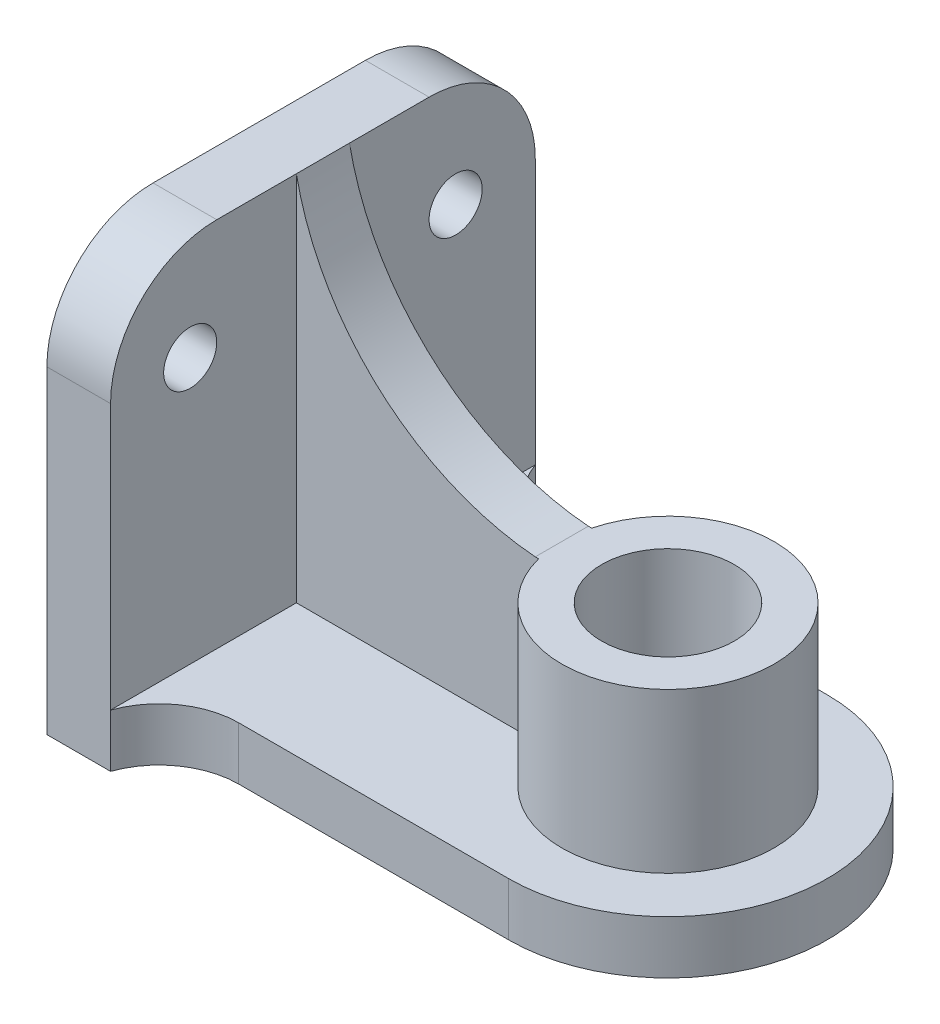
SolidWorks part; units mm, degrees
ref_plane "Front Plane" through (0, 0, 0) normal (0, 0, 1) x (1, 0, 0)
ref_plane "Top Plane" through (0, 0, 0) normal (0, 1, 0) x (1, 0, 0)
ref_plane "Right Plane" through (0, 0, 0) normal (1, 0, 0) x (0, 0, -1)
sketch "Sketch1" plane through (0, 0, 0) normal (0, 1, 0) x (1, 0, 0)
  line L0 (0, 0) -> (0, -80)
  line L1 (0, -80) -> (12, -80)
  line L2 (12, -80) -> (12, 0)
  line L3 (12, 0) -> (0, 0)
  line L4 (77, -1039.1946) -> (77, 48960.8054) construction
  line L5 (-107, -40) -> (107, -40)
  line L6 (77, -70) -> (26.1421, -70)
  line L7 (77, -10) -> (26.1421, -10)
  circle A0 centre (77, -40) radius 20
  circle A1 centre (77, -40) radius 12.5
  arc A2 (77, -70) -> (77, -10) centre (77, -40) ccw
  arc A4 (26.1421, -70) -> (12, -80) centre (26.1421, -85) ccw
  arc A5 (26.1421, -10) -> (12, 0) centre (26.1421, 5) cw
  point P10 (0, -40)
  dimension "D4" = 40
  dimension "D5" = 25
  dimension "D6" = 60
  dimension "D7" = 15
  dimension "D1" = 80
  dimension "D2" = 12
  dimension "D3" = 65
extrude "Boss-Extrude3" add sketch "Sketch1" along normal blind 10 contours L6 L4 A0 L5 L2 A4 | A0 L4 L7 A5 L2 L5 | L4 A0 L5 A2 | L4 A2 L5 A0 region at (39.3253, 0, 23.3734) region at (39.3253, 0, 56.6266) region at (93.1277, 0, 23.8723) region at (93.1277, 0, 56.1277)
extrude "Boss-Extrude4" add sketch "Sketch1<6>" along normal blind 80 contours L0 L5 L2 L3 | L5 L0 L1 L2 region at (6, 0, 20) region at (6, 0, 60)
sketch "Sketch1<6>" plane through (0, 0, 0) normal (0, 1, 0) x (1, 0, 0) same geometry as "Sketch1"
fillet "Fillet1" radius 20 2 edges at (6, 80, 0) (6, 80, 80)
extrude "Boss-Extrude5" add sketch "Sketch1<8>" along normal blind 40 contours L4 A1 L5 A0 | A1 L4 A0 L5 | A0 L4 A1 L5 | L4 A0 L5 A1 region at (66.4713, 0, 29.4713) region at (66.4713, 0, 50.5287) region at (87.5287, 0, 29.4713) region at (87.5287, 0, 50.5287)
sketch "Sketch1<8>" plane through (0, 0, 0) normal (0, 1, 0) x (1, 0, 0) same geometry as "Sketch1"
ref_plane "Plane2" through (12, 0, 0) normal (1, 0, 0) x (0, 0, -1)
sketch "Sketch3" plane through (12, 0, 0) normal (1, 0, 0) x (0, 0, -1)
  line L0 (-45, 80) -> (-45, 10)
  line L1 (-60, 80) -> (-20, 80) construction
  line L2 (-10, 10) -> (-70, 10) construction
  line L3 (-40, 80) -> (-40, 10) construction
  line L4 (-35, 80) -> (-35, 10)
  dimension "D1" = 10
ref_plane "Plane3" through (0, 0, 80) normal (0, 0, 1) x (1, 0, 0)
ref_plane "Plane4" through (57, 0, 0) normal (-1, 0, 0) x (0, 0, 1)
sketch "Sketch6" plane through (57, 0, 0) normal (-1, 0, 0) x (0, 0, 1)
  line L0 (45, 40) -> (45, 10)
  line L1 (45, 80) -> (45, 10) construction
  line L2 (60, 40) -> (20, 40) construction
  line L3 (35, 10) -> (35, 40)
  line L4 (35, 80) -> (35, 10) construction
  line L5 (52.5, 40) -> (27.5, 40) construction
  line L6 (35, 40) -> (45, 40)
  line L7 (45, 10) -> (35, 10)
ref_plane "Plane6" through (0, 0, 45) normal (0, 0, 1) x (1, 0, 0)
sketch "Sketch9" plane through (0, 0, 45) normal (0, 0, 1) x (1, 0, 0)
  line L0 (12, 80) -> (12, 10)
  line L1 (12, 10) -> (57, 10)
  line L2 (57, 10) -> (57, 40)
  arc A0 (12, 80) -> (57, 40) centre (61.0226, 89.8379) ccw
  dimension "D1" = 100
ref_plane "Plane7" through (0, 0, 35) normal (0, 0, 1) x (1, 0, 0)
sketch "Sketch10" plane through (0, 0, 35) normal (0, 0, 1) x (1, 0, 0)
  line L0 (12, 80) -> (12, 10)
  line L1 (12, 10) -> (57, 10)
  line L2 (57, 10) -> (57, 40)
  arc A0 (12, 80) -> (57, 40) centre (61.0226, 89.8379) ccw
  dimension "D1" = 100
ref_plane "Plane8" through (0, 0, 40) normal (0, 0, 1) x (1, 0, 0)
sketch "Sketch11" plane through (0, 0, 40) normal (0, 0, 1) x (1, 0, 0)
  line L0 (12, 80) -> (12, 10)
  line L1 (12, 10) -> (57, 10)
  line L3 (57, 40) -> (57, 10) construction
  line L4 (64.5, 40) -> (64.5, 10)
  line L5 (57, 10) -> (64.5, 10)
  line L6 (57, 40) -> (64.5, 40)
  arc A0 (12, 80) -> (57, 40) centre (61.0226, 89.8379) ccw
  dimension "D1" = 100
extrude "Boss-Extrude11" add sketch "Sketch11" along normal mid plane 10
ref_plane "Plane9" through (12, 0, 0) normal (1, 0, 0) x (0, 0, -1)
sketch "Sketch12" plane through (12, 0, 0) normal (1, 0, 0) x (0, 0, -1)
  line L0 (-60, 80) -> (-45, 80) construction
  line L1 (-80, 60) -> (-80, 10) construction
  line L2 (0, 60) -> (0, 10) construction
  circle A0 centre (-65, 60) radius 5
  circle A1 centre (-15, 60) radius 5
  dimension "D1" = 10
  dimension "D2" = 20
  dimension "D3" = 15
  dimension "D4" = 15
extrude "Cut-Extrude1" cut sketch "Sketch12" against normal through all
